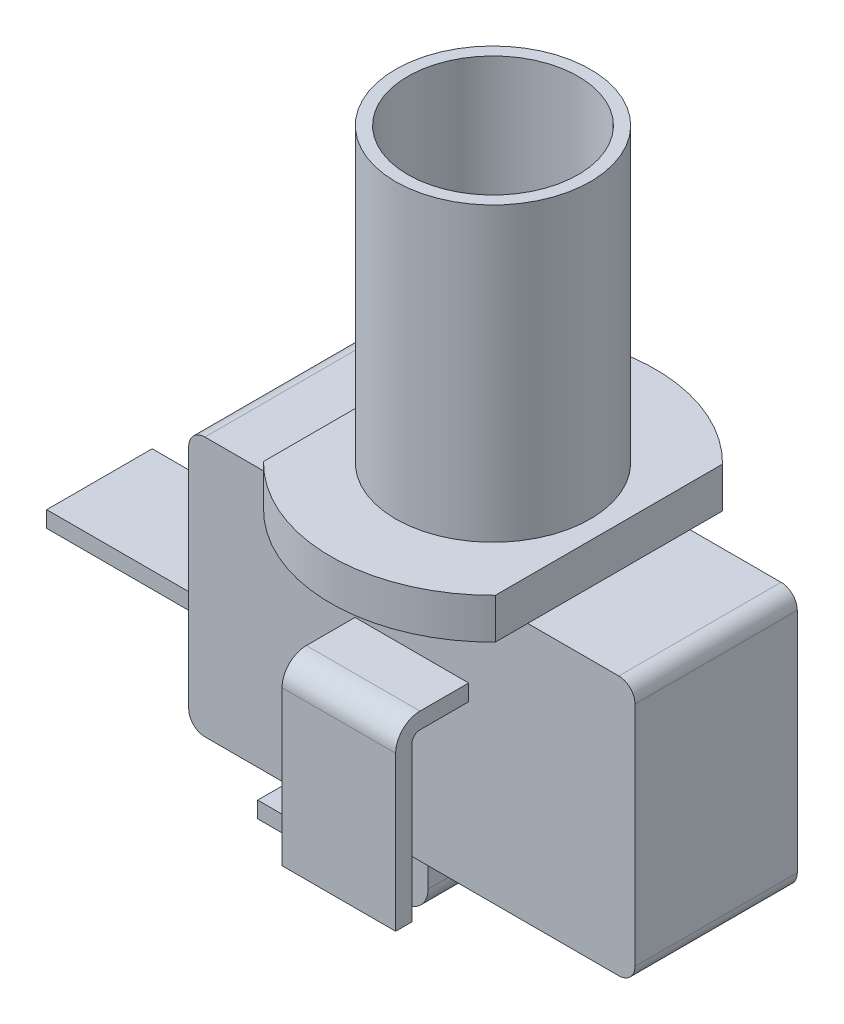
SolidWorks part; units mm, degrees
material "ABS"
ref_plane "Front Plane" through (0, 0, 0) normal (0, 0, 1) x (1, 0, 0)
ref_plane "Top Plane" through (0, 0, 0) normal (0, 1, 0) x (1, 0, 0)
ref_plane "Right Plane" through (0, 0, 0) normal (1, 0, 0) x (0, 0, -1)
sketch "Sketch1" plane through (0, 0, 0) normal (0, 0, 1) x (1, 0, 0)
  line L0 (0, 1) -> (0, 15)
  line L1 (1, 0) -> (26.5, 0)
  line L2 (1, 16) -> (26.5, 16)
  line L3 (27.5, 1) -> (27.5, 15)
  arc A0 (26.5, 16) -> (27.5, 15) centre (26.5, 15) cw
  arc A1 (1, 0) -> (0, 1) centre (1, 1) cw
  arc A2 (26.5, 0) -> (27.5, 1) centre (26.5, 1) ccw
  arc A3 (0, 15) -> (1, 16) centre (1, 15) cw
  point P7 (27.5, 16)
  point P10 (0, 0)
  point P13 (27.5, 0)
  point P16 (0, 16)
  dimension "D3" = 1
  dimension "D1" = 27.5
  dimension "D2" = 16
extrude "Boss-Extrude1" add sketch "Sketch1" along normal blind 5 and the other way blind 5
sketch "Sketch2" plane through (0, 16, 0) normal (0, 1, 0) x (-1, 0, 0)
  line L0 (-13.75, 5) -> (-13.75, -5) construction
  line L1 (-26.5, 5) -> (-1, 5) construction
  line L2 (-26.5, -5) -> (-1, -5) construction
  line L3 (-20.8914, 7) -> (-20.8914, -7)
  line L4 (-6.6086, -7) -> (-6.6086, 7)
  arc A0 (-20.8914, -7) -> (-6.6086, -7) centre (-13.75, 0) ccw
  arc A1 (-6.6086, 7) -> (-20.8914, 7) centre (-13.75, 0) ccw
  dimension "D1" = 20
  dimension "D2" = 14
extrude "Boss-Extrude2" add sketch "Sketch2" along normal blind 2.5
sketch "Sketch3" plane through (0, 0, 0) normal (0, -1, 0) x (1, 0, 0)
  line L0 (13, -3.25) -> (13, 3.25)
  line L1 (13, -3.25) -> (12, -3.25)
  line L2 (13, 3.25) -> (12, 3.25)
  line L3 (12, -3.25) -> (12, 3.25)
  line L4 (0, 5) -> (0, -5) construction
  line L5 (26.5, 0) -> (1, 0) construction
  line L6 (26.5, 5) -> (26.5, -5) construction
  line L7 (1, 5) -> (1, -5) construction
  dimension "D1" = 6.5
  dimension "D2" = 1
  dimension "D3" = 12
sketch "Sketch5" plane through (0, 0, 5) normal (0, 0, 1) x (1, 0, 0)
  line L0 (12, 0) -> (12, -3)
  line L1 (1, 0) -> (26.5, 0) construction
  line L2 (11.5, -3.5) -> (2.5, -3.5)
  line L3 (0, 15) -> (0, 1) construction
  arc A0 (12, -3) -> (11.5, -3.5) centre (11.5, -3) cw
  point P9 (12, -3.5)
  dimension "D4" = 0.5
  dimension "D1" = 9.5
  dimension "D2" = 3.5
  dimension "D3" = 12
sweep "Sweep1" add profiles "Sketch3" path "Sketch5"
sketch "Sketch6" plane through (0, 0, 0) normal (-1, 0, 0) x (0, 0, 1)
  line L0 (-3.25, 5.5) -> (3.25, 5.5)
  line L1 (-3.25, 5.5) -> (-3.25, 4.5)
  line L2 (3.25, 5.5) -> (3.25, 4.5)
  line L3 (-3.25, 4.5) -> (3.25, 4.5)
  line L4 (5, 0) -> (-5, 0) construction
  line L5 (0, 15) -> (0, 1) construction
  line L6 (5, 15) -> (-5, 15) construction
  line L7 (5, 1) -> (-5, 1) construction
  dimension "D1" = 6.5
  dimension "D2" = 1
  dimension "D3" = 4.5
extrude "Boss-Extrude3" add sketch "Sketch6" along normal blind 10.5
sketch "Sketch7" plane through (0, 0, 5) normal (0, 0, 1) x (1, 0, 0)
  line L0 (10.25, 11) -> (17.25, 11)
  line L1 (10.25, 11) -> (10.25, 10)
  line L2 (17.25, 11) -> (17.25, 10)
  line L3 (10.25, 10) -> (17.25, 10)
  line L4 (13.75, 16) -> (13.75, 0) construction
  line L5 (6.6086, 16) -> (20.8914, 16) construction
  line L6 (1, 0) -> (26.5, 0) construction
  dimension "D1" = 7
  dimension "D2" = 10
  dimension "D3" = 1
sketch "Sketch8" plane through (0, 0, 0) normal (-1, 0, 0) x (0, 0, 1)
  line L0 (5, 10) -> (8, 10)
  line L1 (5, 15) -> (5, 1) construction
  line L2 (8.5, 9.5) -> (8.5, 0)
  line L3 (5, 0) -> (-5, 0) construction
  arc A0 (8, 10) -> (8.5, 9.5) centre (8, 9.5) cw
  point P9 (8.5, 10)
  dimension "D4" = 0.5
  dimension "D1" = 3.5
  dimension "D2" = 10
  dimension "D3" = 10
sweep "Sweep2" add profiles "Sketch7" path "Sketch8"
mirror "Mirror1" about plane through (0, 0, 0) normal (0, 0, 1) of "Sweep2"
sketch "Sketch9" plane through (0, 18.5, 0) normal (0, 1, 0) x (-1, 0, 0)
  line L0 (-20.8914, 0) -> (-6.6086, 0) construction
  line L1 (-20.8914, 7) -> (-20.8914, -7) construction
  line L2 (-6.6086, -7) -> (-6.6086, 7) construction
  circle A0 centre (-13.75, 0) radius 6
  dimension "D1" = 12
extrude "Boss-Extrude4" add sketch "Sketch9" along normal blind 18
sketch "Sketch10" plane through (0, 36.5, 0) normal (0, 1, 0) x (1, 0, 0)
  circle A1 centre (13.75, 0) radius 5.25
  dimension "D1" = 10.5
extrude "Cut-Extrude1" cut sketch "Sketch10" against normal up to surface (20.5 mm away) up to face at (23.6957, 16, 0)
